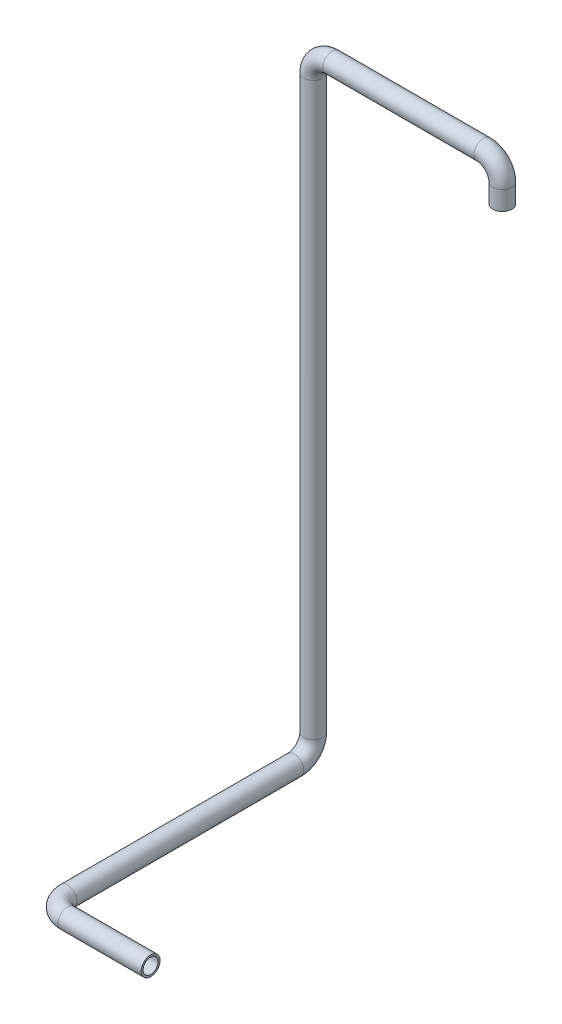
SolidWorks part; units mm, degrees
ref_plane "前视基准面" through (0, 0, 0) normal (0, 0, 1) x (1, 0, 0)
ref_plane "上视基准面" through (0, 0, 0) normal (0, 1, 0) x (1, 0, 0)
ref_plane "右视基准面" through (0, 0, 0) normal (1, 0, 0) x (0, 0, -1)
other "Configuration Table"
sketch "草图1" plane through (0, 0, 0) normal (0, 0, 1) x (1, 0, 0)
  line L0 (0, 0) -> (0, 10)
  line L1 (-10, 20) -> (-90, 20)
  line L2 (-100, 10) -> (-100, -290)
  arc A0 (-90, 20) -> (-100, 10) centre (-90, 10) ccw
  arc A1 (0, 10) -> (-10, 20) centre (-10, 10) ccw
  point P7 (-100, 20)
  point P10 (0, 20)
  dimension "D3" = 10
  dimension "D1" = 20
  dimension "D2" = 100
  dimension "D4" = 310
sweep "扫描-薄件1" add path "草图1" circular profile diameter 10 parameters "D1"=1, "D3"=10
ref_plane "基准面1" through (-100, 0, 0) normal (1, 0, 0) x (0, 0, -1)
sketch "草图2" plane through (-100, 0, 0) normal (1, 0, 0) x (0, 0, -1)
  line L0 (0, -290) -> (0, -292)
  line L1 (-10, -302) -> (-125, -302)
  line L2 (-5, -290) -> (5, -290) construction
  line L3 (10, -302) -> (125, -302) construction
  line L4 (0, -1290) -> (0, 48710) construction
  arc A0 (0, -292) -> (10, -302) centre (10, -292) ccw construction
  arc A1 (0, -292) -> (-10, -302) centre (-10, -292) cw
  point P8 (0, -302)
  dimension "D3" = 10
  dimension "D1" = 125
  dimension "D2" = 12
sweep "扫描-薄件2" add path "草图2" circular profile diameter 10 parameters "D1"=1, "D3"=10
ref_plane "基准面2" through (0, -302, 0) normal (0, 1, 0) x (1, 0, 0)
sketch "草图10" plane through (0, -302, 0) normal (0, 1, 0) x (1, 0, 0)
  line L0 (-100, -125) -> (-100, -130)
  line L2 (-105, -125) -> (-95, -125) construction
  line L3 (-90, -140) -> (-46, -140)
  arc A0 (-100, -130) -> (-90, -140) centre (-90, -130) ccw
  point P7 (-100, -140)
  dimension "D3" = 10
  dimension "D1" = 15
  dimension "D2" = 54
sweep "扫描-薄件3" add path "草图10" circular profile diameter 10 parameters "D1"=1, "D3"=10
